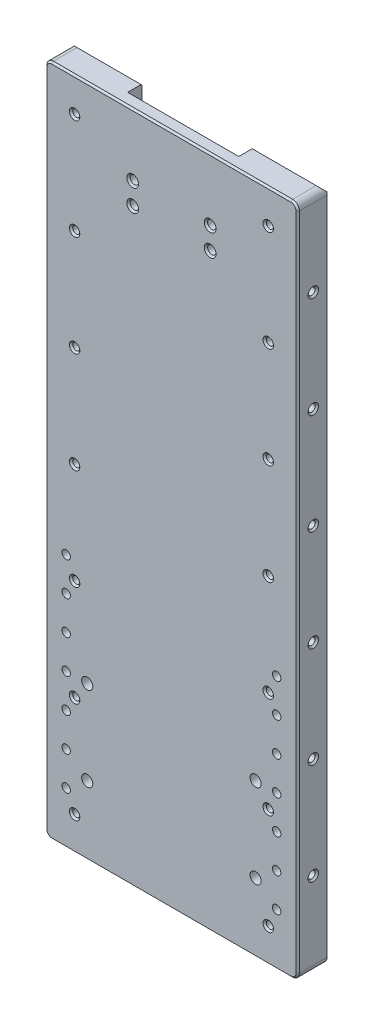
SolidWorks part; units mm, degrees
ref_plane "Front Plane" through (0, 0, 0) normal (0, 0, 1) x (1, 0, 0)
ref_plane "Top Plane" through (0, 0, 0) normal (0, 1, 0) x (1, 0, 0)
ref_plane "Right Plane" through (0, 0, 0) normal (1, 0, 0) x (0, 0, -1)
sketch "Sketch1" plane through (0, 0, 0) normal (0, 0, 1) x (1, 0, 0)
  line L1 (-14, 300) -> (136, 300)
  line L2 (-14, 300) -> (-14, -100)
  line L3 (-14, -100) -> (136, -100)
  line L4 (136, 300) -> (136, -100)
  dimension "D1" = 400
  dimension "D2" = 150
extrude "Boss-Extrude1" add sketch "Sketch1" along normal blind 18.5
sketch "Sketch10" plane through (0, 0, 18.5) normal (0, 0, 1) x (1, 0, 0)
  line L3 (104.1092, 305) -> (136, 300)
  line L4 (136, 300) -> (-14, 300)
  line L6 (17.8908, 305) -> (-14, 300)
  line L8 (61, 305) -> (17.8908, 305)
  line L9 (61, 305) -> (104.1092, 305)
sketch "Sketch2" plane through (0, 0, 0) normal (0, 0, 1) x (1, 0, 0)
  line L1 (94, 272) -> (94, 300)
  line L2 (28, 270) -> (28, 240)
  line L3 (28, 240) -> (94, 240)
  line L4 (94, 240) -> (94, 270)
  line L6 (28, 272) -> (28, 270)
  line L7 (94, 272) -> (94, 270)
  line L8 (136, 300) -> (-14, 300) construction
  line L9 (94, 300) -> (28, 300)
  line L10 (28, 300) -> (28, 272)
extrude "Cut-Extrude1" cut sketch "Sketch2" along normal blind 11.5
fillet "Fillet1" radius 4 2 edges at (94, 240, 5.75) (28, 240, 5.75)
sketch "Sketch6" plane through (0, 0, 0) normal (0, 0, -1) x (-1, 0, 0)
  line L1 (-42, 240) -> (-42, 300)
  line L17 (-136, 300) -> (-94, 300) construction
  line L21 (-80, 240) -> (-80, 300)
  line L24 (-80, 240) -> (-80, 50)
  line L25 (-80, 50) -> (-80, 44)
  line L26 (-42, 50) -> (-42, 240)
  line L27 (-42, 50) -> (-42, 44)
  line L28 (-42, 44) -> (-42, -9)
  line L29 (-42, -25) -> (-42, -9)
  line L30 (-80, -25) -> (-42, -25)
  line L31 (-80, -9) -> (-80, -25)
  line L32 (-80, -9) -> (-80, 44)
  line L35 (-80, 300) -> (-42, 300)
extrude "Cut-Extrude3" cut sketch "Sketch6" against normal blind 8
sketch "Sketch7" plane through (0, 0, 11.5) normal (0, 0, -1) x (-1, 0, 0)
  circle A4 centre (-84, 263) radius 3.3
  circle A5 centre (-84, 250) radius 3.3
  circle A6 centre (-38, 250) radius 3.3
  circle A7 centre (-38, 263) radius 3.3
hole_wizard "M6x1.0 Tapped Hole1" positions "Sketch8" profile "Sketch9" tap size "M6x1.0" standard "ANSI Metric"
sketch "Sketch8" plane through (0, 0, 11.5) normal (0, 0, -1) x (-1, 0, 0)
  point P12 (-84, 263)
  point P15 (-38, 263)
  point P18 (-38, 250)
  point P21 (-84, 250)
sketch "Sketch9" plane through (84, 263, 11.5) normal (1, 0, 0) x (0, 1, 0)
  line L0 (0, 0) -> (0, 15)
  line L1 (0, 15) -> (2.5, 13.4978)
  line L2 (2.5, 13.4978) -> (2.5, 0)
  line L5 (2.5, 0) -> (0, 0)
  line L10 (0, 15) -> (-2.5, 13.4978) construction
  line L11 (0, -6.35) -> (0, 107.95) construction
  dimension "Tap Drill Dia." = 5
  dimension "Tap Drill Depth" = 15
  dimension "Drill Angle" = 118
cosmetic thread "Hole Thread7"
cosmetic thread "Hole Thread8"
cosmetic thread "Hole Thread9"
cosmetic thread "Hole Thread10"
sketch "Sketch11" plane through (0, 0, 0) normal (0, 0, -1) x (-1, 0, 0)
  line L2 (-61, 262) -> (-79, 262)
  line L3 (-61, 262) -> (-43, 262)
  line L4 (-43, 262) -> (-43, 273)
  line L5 (-47, 277) -> (-75, 277)
  line L6 (-79, 273) -> (-79, 262)
  arc A0 (-43, 273) -> (-47, 277) centre (-47, 273) ccw
  arc A1 (-75, 277) -> (-79, 273) centre (-75, 273) ccw
  dimension "D1" = 4
sketch "Sketch12" plane through (0, 0, 0) normal (0, 0, -1) x (-1, 0, 0)
  line L0 (-3.5, -80) -> (-3.5, 280) construction
  line L1 (-118.5, -80) -> (-118.5, 280) construction
  line L2 (-3.5, -80) -> (-3.5, 280)
  line L3 (-118.5, -80) -> (-118.5, 280)
  circle A0 centre (-118.5, 280) radius 2.5
  circle A1 centre (-3.5, 280) radius 2.5
  circle A2 centre (-3.5, 220) radius 2.5
  circle A3 centre (-3.5, 160) radius 2.5
  circle A4 centre (-3.5, 100) radius 2.5
  circle A5 centre (-3.5, 40) radius 2.5
  circle A6 centre (-3.5, -20) radius 2.5
  circle A7 centre (-3.5, -80) radius 2.5
  circle A8 centre (-118.5, 220) radius 2.5
  circle A9 centre (-118.5, 160) radius 2.5
  circle A10 centre (-118.5, 100) radius 2.5
  circle A11 centre (-118.5, 40) radius 2.5
  circle A12 centre (-118.5, -20) radius 2.5
  circle A13 centre (-118.5, -80) radius 2.5
  dimension "D1" = 2
  dimension "D2" = 7
hole_wizard "M5x0.8 Tapped Hole1" positions "Sketch13" profile "Sketch14" tap size "M5x0.8" standard "ANSI Metric" end condition through all
sketch "Sketch13" plane through (0, 0, 0) normal (0, 0, -1) x (-1, 0, 0)
  point P0 (-118.5, 280)
  point P3 (-3.5, 280)
  point P6 (-118.5, 220)
  point P9 (-3.5, 220)
  point P12 (-3.5, 160)
  point P15 (-118.5, 160)
  point P18 (-118.5, 100)
  point P21 (-3.5, 100)
  point P24 (-3.5, 40)
  point P27 (-118.5, 40)
  point P30 (-3.5, -20)
  point P33 (-118.5, -20)
  point P36 (-118.5, -80)
  point P39 (-3.5, -80)
sketch "Sketch14" plane through (118.5, 280, 0) normal (1, 0, 0) x (0, 1, 0)
  line L0 (0, 0) -> (0, 18.5)
  line L1 (0, 18.5) -> (2.1, 18.5)
  line L2 (2.1, 18.5) -> (2.1, 0)
  line L5 (2.1, 0) -> (0, 0)
  line L11 (0, -6.35) -> (0, 107.95) construction
  dimension "Thru Tap Drill Dia." = 4.2
  dimension "Thru Tap Drill Depth" = 18.5
cosmetic thread "Hole Thread11"
cosmetic thread "Hole Thread12"
cosmetic thread "Hole Thread13"
cosmetic thread "Hole Thread14"
cosmetic thread "Hole Thread15"
cosmetic thread "Hole Thread16"
cosmetic thread "Hole Thread17"
cosmetic thread "Hole Thread18"
cosmetic thread "Hole Thread19"
cosmetic thread "Hole Thread20"
cosmetic thread "Hole Thread21"
cosmetic thread "Hole Thread22"
cosmetic thread "Hole Thread23"
cosmetic thread "Hole Thread24"
fillet "Fillet5" radius 4 4 edges at (-14, -100, 9.25) (136, -100, 9.25) (136, 300, 9.25) (-14, 300, 9.25)
chamfer "Chamfer2" distance 1 angle 45 26 edges at (-12.8284, 298.8284, 18.5) (61, 300, 18.5) (134.8284, 298.8284, 18.5) (136, 100, 18.5) (134.8284, -98.8284, 18.5) (61, -100, 18.5) (-12.8284, -98.8284, 18.5) (-14, 100, 18.5) (86.5, 250, 18.5) (40.5, 250, 18.5) (40.5, 263, 18.5) (86.5, 263, 18.5) (1.4, -80, 18.5) (116.4, -80, 18.5) (116.4, -20, 18.5) (1.4, -20, 18.5) (116.4, 40, 18.5) (1.4, 40, 18.5) (1.4, 100, 18.5) (116.4, 100, 18.5) (116.4, 160, 18.5) (1.4, 160, 18.5) (1.4, 220, 18.5) (116.4, 220, 18.5) (1.4, 280, 18.5) (116.4, 280, 18.5)
fillet "Fillet6" radius 4 4 edges at (42, 240, 4) (80, 240, 4) (42, -25, 4) (80, -25, 4)
chamfer "Chamfer4" distance 3.5 angle 45 2 edges at (113, 300, 0) (9, 300, 0)
chamfer "Chamfer5" distance 1 angle 45 7 edges at (135.9921, 296.2505, 0) (136, 100, 0) (134.8284, -98.8284, 0) (61, -100, 0) (-13.9921, 296.2505, 0) (-12.8284, -98.8284, 0) (-14, 100, 0)
sketch "Sketch15" plane through (-14, 0, 0) normal (-1, 0, 0) x (0, 0, 1)
  circle A0 centre (9.25, 250) radius 2.1
  circle A1 centre (9.25, 190) radius 2.1
  circle A2 centre (9.25, 130) radius 2.1
  circle A3 centre (9.25, 70) radius 2.1
  circle A4 centre (9.25, 10) radius 2.1
  circle A5 centre (9.25, -50) radius 2.1
sketch "Sketch16" plane through (136, 0, 0) normal (1, 0, 0) x (0, 0, -1)
  circle A0 centre (-9.25, 250) radius 2.1
  circle A1 centre (-9.25, 190) radius 2.1
  circle A2 centre (-9.25, 130) radius 2.1
  circle A3 centre (-9.25, 70) radius 2.1
  circle A4 centre (-9.25, 10) radius 2.1
  circle A5 centre (-9.25, -50) radius 2.1
extrude "Cut-Extrude5" cut sketch "Sketch15" against normal blind 17
extrude "Cut-Extrude6" cut sketch "Sketch16" against normal blind 17
chamfer "Chamfer6" distance 1 angle 45 26 edges at (-14, -52.1, 9.25) (-14, 7.9, 9.25) (-14, 67.9, 9.25) (-14, 127.9, 9.25) (-14, 187.9, 9.25) (-14, 247.9, 9.25) (136, 252.1, 9.25) (136, 192.1, 9.25) (136, 132.1, 9.25) (136, 72.1, 9.25) (136, 12.1, 9.25) (136, -47.9, 9.25) (1.4, -80, 0) (116.4, -80, 0) (1.4, -20, 0) (116.4, -20, 0) (1.4, 40, 0) (116.4, 40, 0) (1.4, 100, 0) (116.4, 100, 0) (116.4, 160, 0) (116.4, 220, 0) (1.4, 220, 0) (1.4, 280, 0) (116.4, 280, 0) (1.4, 160, 0)
sketch "Sketch17" plane through (0, 0, 0) normal (0, 0, -1) x (-1, 0, 0)
  circle A0 centre (-96, 292) radius 2.1
  circle A1 centre (-96, 280) radius 2.1
  circle A2 centre (-26, 292) radius 2.1
  circle A3 centre (-26, 280) radius 2.1
sketch "Sketch18" plane through (0, 0, 18.5) normal (0, 0, 1) x (1, 0, 0)
  circle A0 centre (123.5, -69) radius 2.5
  circle A1 centre (-1.5, -69) radius 2.5
  circle A2 centre (-1.5, -49) radius 2.5
  circle A3 centre (-1.5, -29) radius 2.5
  circle A4 centre (-1.5, -9) radius 2.5
  circle A5 centre (123.5, -49) radius 2.5
  circle A6 centre (123.5, -29) radius 2.5
  circle A7 centre (123.5, -9) radius 2.5
  circle A8 centre (123.5, 11) radius 2.5
  circle A9 centre (-1.5, 11) radius 2.5
  circle A10 centre (123.5, 31) radius 2.5
  circle A11 centre (-1.5, 31) radius 2.5
  circle A12 centre (123.5, 51) radius 2.5
  circle A13 centre (-1.5, 51) radius 2.5
  circle A14 centre (111, -59) radius 3.3
  circle A15 centre (11, -59) radius 3.3
  circle A16 centre (11, -9) radius 3.3
  circle A17 centre (111, -9) radius 3.3
  dimension "D1" = 2
  dimension "D3" = 2
  dimension "D2" = 7
  dimension "D4" = 2
extrude "Cut-Extrude7" cut sketch "Sketch18" against normal through all
sketch "Sketch19" plane through (0, 0, 11.5) normal (0, 0, -1) x (-1, 0, 0)
  line L0 (-94, 244) -> (-94, 300) construction
  line L1 (-32, 240) -> (-90, 240) construction
  line L2 (-28, 300) -> (-28, 244) construction
  line L3 (-94, 244) -> (-94, 300)
  line L4 (-32, 240) -> (-90, 240)
  line L5 (-28, 300) -> (-28, 244)
  line L6 (-94, 300) -> (-94, 305)
  line L7 (-94, 305) -> (-28, 305)
  line L8 (-28, 305) -> (-28, 300)
  arc A0 (-94, 244) -> (-90, 240) centre (-90, 244) ccw construction
  arc A1 (-32, 240) -> (-28, 244) centre (-32, 244) ccw construction
  arc A2 (-94, 244) -> (-90, 240) centre (-90, 244) ccw
  arc A3 (-32, 240) -> (-28, 244) centre (-32, 244) ccw
sketch "Sketch21" plane through (0, 0, 0) normal (0, 0, -1) x (-1, 0, 0)
  line L2 (-71, -28) -> (-71, -58)
  line L3 (-71, -58) -> (-51, -58)
  line L4 (-51, -58) -> (-51, -28)
  line L7 (-71, -25) -> (-51, -25)
  line L8 (-71, -28) -> (-71, -25)
  line L9 (-71, -25) -> (-51, -25)
  line L10 (-51, -25) -> (-51, -28)
  line L11 (-28, 244) -> (-28, -13.4252)
  line L12 (-28, -13.4252) -> (-42, -13.4252)
  line L13 (-42, -21) -> (-42, 236) construction
  line L14 (-42, -13.4252) -> (-42, 244)
  line L15 (-42, 244) -> (-28, 244)
extrude "Cut-Extrude9" cut sketch "Sketch21" against normal blind 4 contours L10 L7 L8 L2 L3 L4 | L15 L14 L12 L11
fillet "Fillet7" radius 5 6 edges at (71, -58, 2) (51, -58, 2) (51, -25, 2) (71, -25, 2) (28, -13.4252, 2) (42, -13.4252, 2)
chamfer "Chamfer8" distance 3 angle 45 19 edges at (94, 270.25, 0) (92.8284, 241.1716, 0) (87, 240, 0) (81.1716, 238.8284, 0) (80, 107.5, 0) (78.8284, -23.8284, 0) (72.4645, -26.4645, 0) (71, -41.5, 0) (69.5355, -56.5355, 0) (61, -58, 0) (52.4645, -56.5355, 0) (28, 144.0374, 0) (51, -41.5, 0) (49.5355, -26.4645, 0) (43.1716, -23.8284, 0) (42, -19.7126, 0) (29.4645, -11.9607, 0) (35, -13.4252, 0) (40.5355, -14.8896, 0)
sketch "Sketch23" plane through (0, 0, 4) normal (0, 0, -1) x (-1, 0, 0)
  line L4 (-42, -18.4252) -> (-48, -18.4252)
  line L5 (-32, 246) -> (-28, 246)
  line L6 (-48, -18.4252) -> (-48, 236)
  line L7 (-38, 246) -> (-32, 246)
  line L8 (-48, -18.4252) -> (-48, 236)
  line L9 (-38, 246) -> (-32, 246)
  line L10 (-28, 246) -> (-28, 244)
  line L12 (-37, -13.4252) -> (-33, -13.4252)
  line L13 (-28, -8.4252) -> (-28, 244)
  line L14 (-32, 240) -> (-38, 240)
  line L15 (-42, 236) -> (-42, -18.4252)
  line L16 (-37, -13.4252) -> (-33, -13.4252)
  line L17 (-28, -8.4252) -> (-28, 244)
  line L20 (-46, -19) -> (-46, -25)
  line L21 (-76, -19) -> (-46, -19)
  line L22 (-76, -19) -> (-46, -19)
  line L23 (-76, -19) -> (-76, -25)
  line L26 (-71, -30) -> (-71, -53)
  line L27 (-66, -58) -> (-56, -58)
  line L28 (-51, -53) -> (-51, -30)
  line L29 (-46, -25) -> (-76, -25)
  line L30 (-71, -30) -> (-71, -53)
  line L31 (-66, -58) -> (-56, -58)
  line L32 (-51, -53) -> (-51, -30)
  arc A8 (-38, 246) -> (-48, 236) centre (-38, 236) ccw
  arc A9 (-38, 246) -> (-48, 236) centre (-38, 236) ccw
  arc A12 (-33, -13.4252) -> (-28, -8.4252) centre (-33, -8.4252) ccw
  arc A13 (-32, 240) -> (-28, 244) centre (-32, 244) ccw
  arc A14 (-38, 240) -> (-42, 236) centre (-38, 236) ccw
  arc A15 (-37, -13.4252) -> (-42, -18.4252) centre (-37, -18.4252) ccw
  arc A16 (-33, -13.4252) -> (-28, -8.4252) centre (-33, -8.4252) ccw
  arc A19 (-37, -13.4252) -> (-42, -18.4252) centre (-37, -18.4252) ccw
  arc A20 (-71, -53) -> (-66, -58) centre (-66, -53) ccw
  arc A21 (-56, -58) -> (-51, -53) centre (-56, -53) ccw
  arc A22 (-46, -25) -> (-51, -30) centre (-46, -30) ccw
  arc A23 (-71, -30) -> (-76, -25) centre (-76, -30) ccw
  arc A24 (-71, -53) -> (-66, -58) centre (-66, -53) ccw
  arc A25 (-56, -58) -> (-51, -53) centre (-56, -53) ccw
  arc A26 (-46, -25) -> (-51, -30) centre (-46, -30) ccw
  arc A27 (-71, -30) -> (-76, -25) centre (-76, -30) ccw
  dimension "D3" = 6
  dimension "D1" = 6
  dimension "D2" = 0
  dimension "D4" = 0
